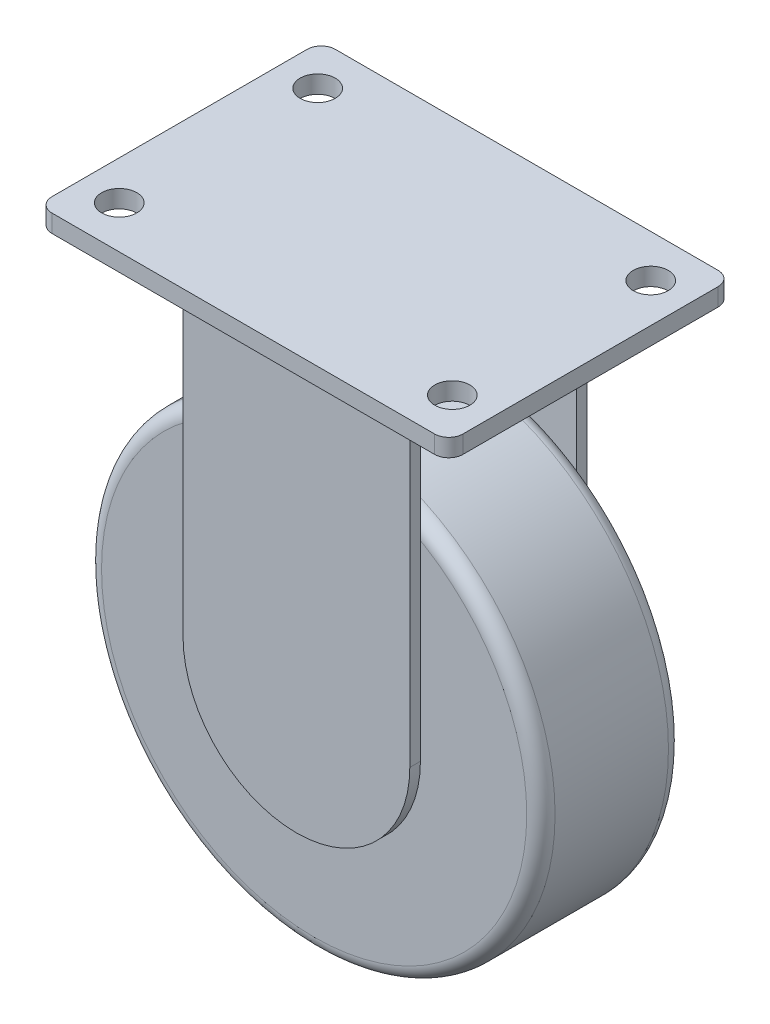
SolidWorks part; units mm, degrees
ref_plane "Front" through (0, 0, 0) normal (0, 0, 1) x (1, 0, 0)
ref_plane "Top" through (0, 0, 0) normal (0, 1, 0) x (1, 0, 0)
ref_plane "Right" through (0, 0, 0) normal (1, 0, 0) x (0, 0, -1)
sketch "Sketch1" plane through (0, 0, 0) normal (0, 1, 0) x (1, 0, 0)
  line L0 (-37.3062, 22.225) -> (37.3062, -22.225) construction
  line L1 (-46.0375, 31.75) -> (46.0375, 31.75)
  line L2 (-46.0375, 31.75) -> (-46.0375, -31.75)
  line L3 (-46.0375, -31.75) -> (46.0375, -31.75)
  line L4 (46.0375, 31.75) -> (46.0375, -31.75)
  line L5 (-46.0375, -31.75) -> (46.0375, 31.75) construction
  circle A0 centre (-37.3062, 22.225) radius 3.937
  circle A1 centre (-37.3062, -22.225) radius 3.937
  circle A2 centre (37.3062, -22.225) radius 3.937
  circle A3 centre (37.3062, 22.225) radius 3.937
  dimension "D3" = 7.874
  dimension "D4" = 44.45
  dimension "D5" = 74.6125
  dimension "D1" = 63.5
  dimension "D2" = 92.075
extrude "Extrude1" add sketch "Sketch1" along normal blind 3.9688
sketch "Sketch2" plane through (0, 0, 0) normal (0, 1, 0) x (-1, 0, 0)
  line L0 (0, -17.4625) -> (0, 17.4625) construction
  line L1 (25.4, 19.8438) -> (-25.4, 19.8438)
  line L2 (25.4, 19.8438) -> (25.4, 17.4625)
  line L3 (25.4, 17.4625) -> (-25.4, 17.4625)
  line L4 (-25.4, 19.8438) -> (-25.4, 17.4625)
  line L5 (25.4, -17.4625) -> (-25.4, -17.4625)
  line L6 (25.4, -17.4625) -> (25.4, -19.8438)
  line L7 (25.4, -19.8438) -> (-25.4, -19.8438)
  line L8 (-25.4, -17.4625) -> (-25.4, -19.8438)
  dimension "D1" = 2.3813
  dimension "D2" = 50.8
  dimension "D3" = 34.925
extrude "Extrude2" add sketch "Sketch2" against normal blind 100.8063
fillet "Fillet1" radius 25.4 4 edges at (-25.4, -100.8063, 18.6531) (-25.4, -100.8063, -18.6531) (25.4, -100.8063, -18.6531) (25.4, -100.8063, 18.6531)
sketch "Sketch3" plane through (0, 0, 0) normal (0, 0, 1) x (1, 0, 0)
  circle A0 centre (0, -75.4063) radius 6.35
  dimension "D1" = 12.7
extrude "Extrude3" add sketch "Sketch3" along normal up to next and the other way up to next
sketch "Sketch4" plane through (0, 0, 0) normal (0, 0, 1) x (1, 0, 0)
  circle A0 centre (0, -75.4063) radius 50.8
  dimension "D1" = 101.6
extrude "Extrude4" add sketch "Sketch4" along normal mid plane 31.75
fillet "Fillet2" radius 3.175 2 edges at (50.8, -75.4063, -15.875) (50.8, -75.4063, 15.875)
fillet "Fillet3" radius 3.175 4 edges at (-46.0375, 1.9844, -31.75) (46.0375, 1.9844, -31.75) (46.0375, 1.9844, 31.75) (-46.0375, 1.9844, 31.75)
